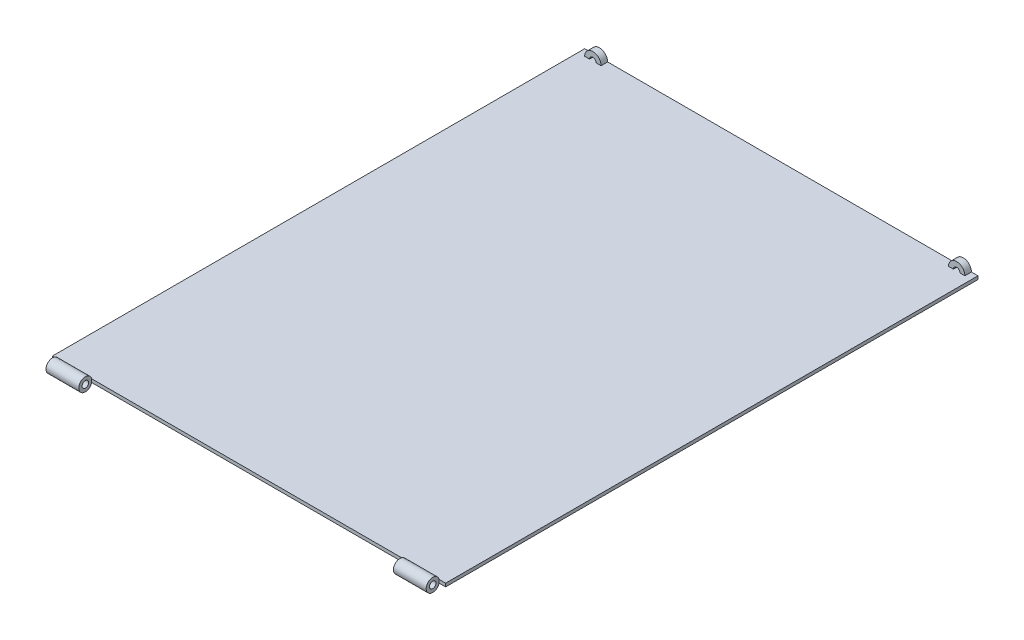
SolidWorks part; units mm, degrees
material "PLA Aero Bambu"
ref_plane "Front Plane" through (0, 0, 0) normal (0, 0, 1) x (1, 0, 0)
ref_plane "Top Plane" through (0, 0, 0) normal (0, 1, 0) x (1, 0, 0)
ref_plane "Right Plane" through (0, 0, 0) normal (1, 0, 0) x (0, 0, -1)
sketch "Sketch1" plane through (0, 0, 0) normal (0, 1, 0) x (1, 0, 0)
  line L1 (-30, 41.09) -> (30, 41.09)
  line L2 (-30, 41.09) -> (-30, -41.09)
  line L3 (-30, -41.09) -> (30, -41.09)
  line L4 (30, 41.09) -> (30, -41.09)
  point P4 (0, -41.09)
  point P6 (-30, 0)
  dimension "D1" = 60
  dimension "D2" = 82.18
extrude "Boss-Extrude1" add sketch "Sketch1" along normal blind 0.5
sketch "Sketch3" plane through (0, 0, 0) normal (1, 0, 0) x (0, 0, -1)
  line L0 (-41.09, 0.5) -> (-41.09, 0) construction
  circle A0 centre (-41.09, 0.25) radius 0.5
  circle A1 centre (-41.09, 0.25) radius 1
  dimension "D1" = 1
  dimension "D2" = 2
extrude "Boss-Extrude2" add sketch "Sketch3" along normal up to surface and the other way up to surface up to face at (30, 0.25, 0) other way up to face at (-30, 0.25, 0)
sketch "Sketch4" plane through (-30, 0, 0) normal (-1, 0, 0) x (0, 0, 1)
  line L0 (41.09, 0.5) -> (41.09, 0) construction
  circle A0 centre (41.09, 0.25) radius 0.5
  arc A1 (40.657, 0) -> (40.657, 0.5) centre (41.09, 0.25) ccw construction
extrude "Cut-Extrude1" cut sketch "Sketch4" against normal through all
sketch "Sketch5" plane through (0, 0.5, 0) normal (0, 1, 0) x (1, 0, 0)
  line L0 (-30, -40.1218) -> (30, -40.1218) construction
  line L1 (-24, -40.1218) -> (24, -40.1218)
  line L2 (-24, -40.1218) -> (-24, -42.09)
  line L3 (-24, -42.09) -> (24, -42.09)
  line L4 (24, -40.1218) -> (24, -42.09)
  line L5 (-30, -42.09) -> (30, -42.09) construction
  line L9 (-30, -40.1218) -> (-29, -40.1218)
  line L10 (-30, -40.1218) -> (-30, -42.09)
  line L11 (-30, -42.09) -> (-29, -42.09)
  line L12 (-29, -40.1218) -> (-29, -42.09)
  line L13 (30, -40.1218) -> (29, -40.1218)
  line L14 (30, -40.1218) -> (30, -42.09)
  line L15 (30, -42.09) -> (29, -42.09)
  line L16 (29, -40.1218) -> (29, -42.09)
  point P18 (-29, -41.1059)
  dimension "D1" = 1
  dimension "D2" = 5
  dimension "D3" = 5
extrude "Cut-Extrude2" cut sketch "Sketch5" against normal through all and the other way through all
sketch "Sketch7" plane through (0, 0, -41.09) normal (0, 0, -1) x (-1, 0, 0)
  line L0 (-24, 0.5) -> (-29, 0.5) construction
  line L1 (-30, 0.5) -> (30, 0.5) construction
  line L2 (-29, 0.5) -> (-28.25, 0.5)
  line L3 (-27.25, 0.5) -> (-26.5, 0.5)
  arc A0 (-29, 0.5) -> (-26.5, 0.5) centre (-27.75, 0.5) cw
  arc A1 (-28.25, 0.5) -> (-27.25, 0.5) centre (-27.75, 0.5) cw
  point P1 (0, 0)
  point P9 (-28.5526, 0.5)
  dimension "D1" = 0.75
extrude "Boss-Extrude3" add sketch "Sketch7" against normal blind 1
mirror "Mirror1" about plane through (0, 0, 0) normal (1, 0, 0) of "Boss-Extrude3"
